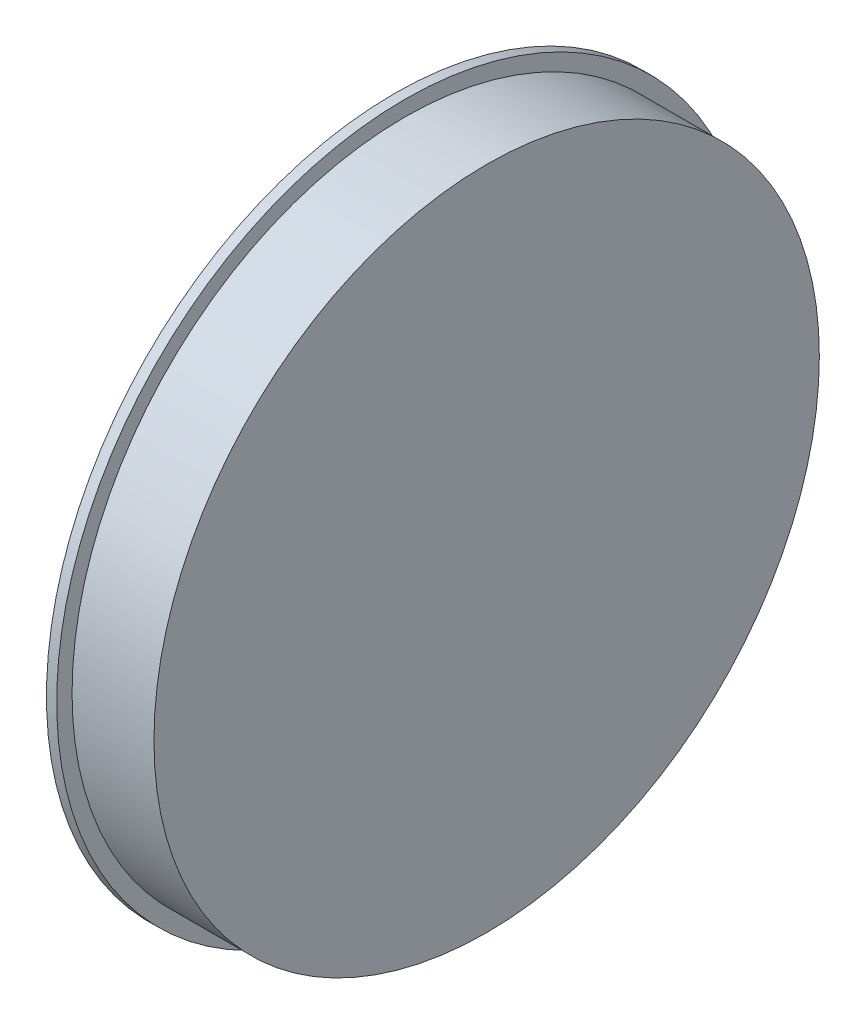
SolidWorks part; units mm, degrees
ref_plane "Front Plane" through (0, 0, 0) normal (0, 0, 1) x (1, 0, 0)
ref_plane "Top Plane" through (0, 0, 0) normal (0, 1, 0) x (1, 0, 0)
ref_plane "Right Plane" through (0, 0, 0) normal (1, 0, 0) x (0, 0, -1)
sketch "Sketch1" plane through (0, 0, 0) normal (0, 0, 1) x (1, 0, 0)
  line L6 (0, 0) -> (0, 34)
  line L7 (0, 34) -> (1, 34)
  line L8 (1, 34) -> (1, 32.5)
  line L9 (1, 32.5) -> (9, 32.5)
  line L10 (9, 32.5) -> (9, 0)
  line L11 (9, 0) -> (0, 0)
  dimension "D1" = 32.5
  dimension "D2" = 9
  dimension "D3" = 1
  dimension "D4" = 34
revolve "Revolve1" add sketch "Sketch1" angle 360 about L11
ref_axis "Axis1" through (1, 0, 0) along (1, 0, 0)
